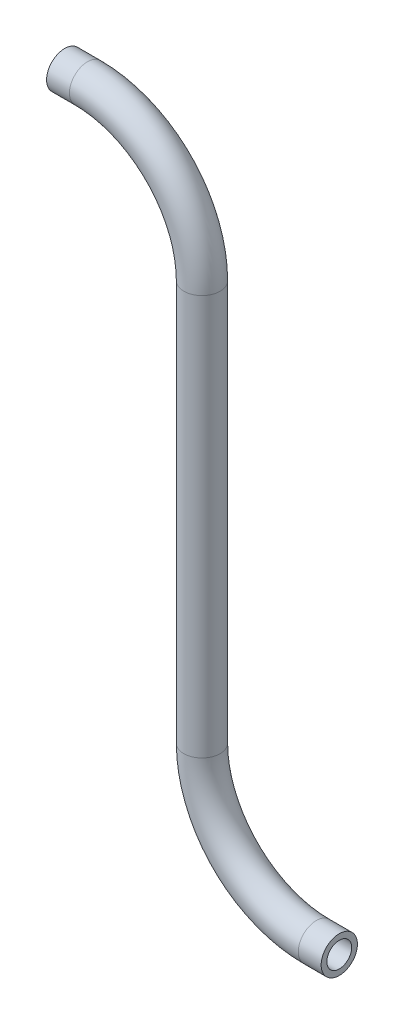
SolidWorks part; units mm, degrees
ref_plane "Piano frontale" through (0, 0, 0) normal (0, 0, 1) x (1, 0, 0)
ref_plane "Piano superiore" through (0, 0, 0) normal (0, 1, 0) x (1, 0, 0)
ref_plane "Piano destro" through (0, 0, 0) normal (1, 0, 0) x (0, 0, -1)
sketch "Schizzo1" plane through (0, 0, 0) normal (0, 0, 1) x (1, 0, 0)
  line L0 (0, 10) -> (0, 45)
  line L1 (-10, 55) -> (-12, 55)
  line L2 (10, 0) -> (12, 0)
  arc A0 (0, 45) -> (-10, 55) centre (-10, 45) ccw
  arc A1 (0, 10) -> (10, 0) centre (10, 10) ccw
  point P7 (0, 55)
  point P10 (0, 0)
  dimension "D3" = 10
  dimension "D1" = 55
  dimension "D2" = 12
  dimension "D4" = 90
  dimension "D5" = 90
sweep "Sweep-Sottile1" add path "Schizzo1" circular profile diameter 3.17 parameters "D1"=0.5, "D3"=3.17
